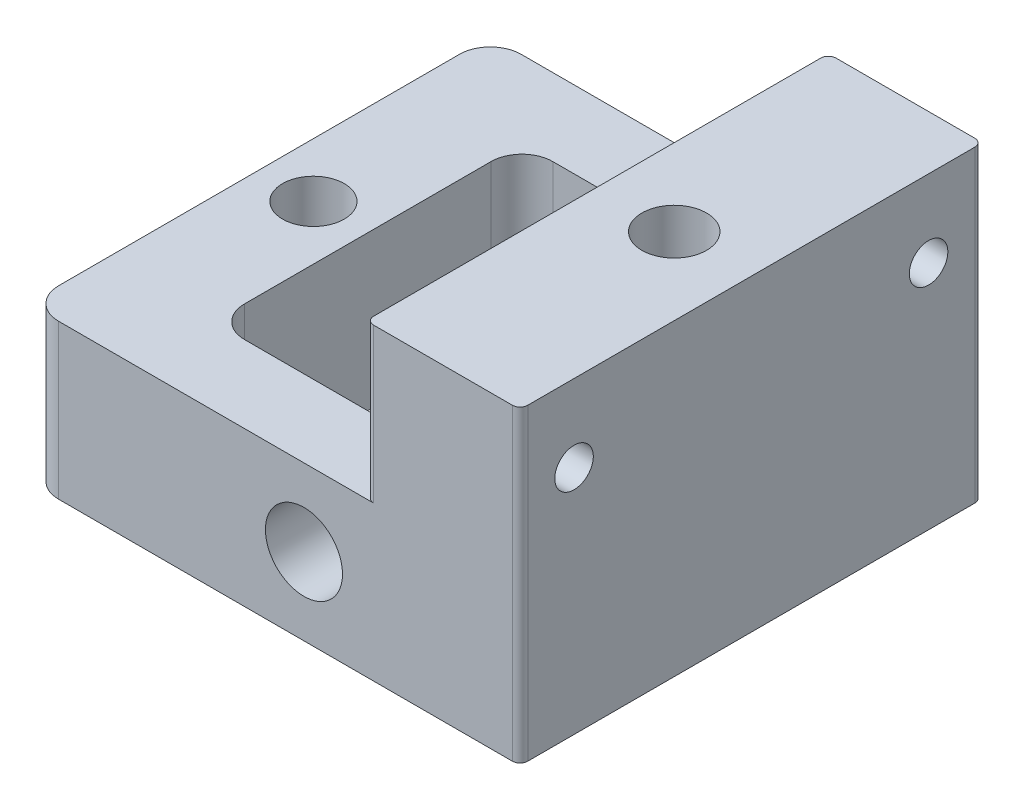
SolidWorks part; units mm, degrees
material "AISI 1045 Steel, cold drawn"
ref_plane "Front Plane" through (0, 0, 0) normal (0, 0, 1) x (1, 0, 0)
ref_plane "Top Plane" through (0, 0, 0) normal (0, 1, 0) x (1, 0, 0)
ref_plane "Right Plane" through (0, 0, 0) normal (1, 0, 0) x (0, 0, -1)
sketch "Sketch1" plane through (0, 0, 0) normal (0, 1, 0) x (1, 0, 0)
  line L1 (7.44, -10) -> (-7.44, -10)
  line L2 (7.44, -10) -> (7.44, 10)
  line L3 (7.44, 10) -> (-7.44, 10)
  line L4 (-7.44, -10) -> (-7.44, 10)
  line L5 (7.44, -10) -> (-7.44, 10) construction
  line L6 (7.44, 10) -> (-7.44, -10) construction
  line L7 (17.44, -15) -> (-14.49, -15)
  line L8 (17.44, -15) -> (17.44, 15)
  line L9 (17.44, 15) -> (-14.49, 15)
  line L10 (-14.49, -15) -> (-14.49, 15)
  line L11 (17.44, -15) -> (-14.49, 15) construction
  line L12 (17.44, 15) -> (-14.49, -15) construction
  point P0 (0, 0)
  point P6 (1.475, 0)
  dimension "D1" = 14.88
  dimension "D2" = 20
  dimension "D3" = 7.05
  dimension "D4" = 5
  dimension "D5" = 10
extrude "Boss-Extrude1" add sketch "Sketch1" along normal blind 10
sketch "Sketch2" plane through (0, 10, 0) normal (0, 1, 0) x (1, 0, 0)
  line L0 (-14.49, -15) -> (17.44, -15) construction
  line L1 (17.44, 15) -> (7.44, 15)
  line L2 (17.44, 15) -> (17.44, -15)
  line L3 (17.44, -15) -> (7.44, -15)
  line L4 (7.44, 15) -> (7.44, -15)
  line L5 (7.44, -10) -> (7.44, 10) construction
extrude "Boss-Extrude2" add sketch "Sketch2" along normal blind 10
hole_wizard "Tap Drill for M5x0.8 Tap1" positions "Sketch3" profile "Sketch4" hole size "M5x0.8" standard "ANSI Metric" end condition through all
sketch "Sketch3" plane through (0, 20, 0) normal (0, 1, 0) x (1, 0, 0)
  line L1 (17.44, 15) -> (7.44, -15) construction
  point P0 (12.44, 0)
sketch "Sketch4" plane through (12.44, 20, 0) normal (1, 0, 0) x (0, 0, 1)
  line L0 (0, 0) -> (0, 20)
  line L1 (0, 20) -> (2.1, 20)
  line L2 (2.1, 20) -> (2.1, 0)
  line L5 (2.1, 0) -> (0, 0)
  line L11 (0, -6.35) -> (0, 107.95) construction
  dimension "Thru Hole Dia." = 4.2
  dimension "Thru Hole Depth" = 20
fillet "Fillet2" radius 2 4 edges at (-7.44, 5, 10) (-7.44, 5, -10) (7.44, 5, -10) (7.44, 5, 10)
sketch "Sketch5" plane through (0, 0, -10) normal (0, 0, 1) x (1, 0, 0)
  line L0 (7.44, 10) -> (7.44, 0) construction
  line L1 (5.44, 10) -> (-5.44, 10) construction
  circle A0 centre (3.42, 5) radius 2.5
  dimension "D2" = 5
  dimension "D1" = 4.02
  dimension "D3" = 5
extrude "Cut-Extrude2" cut sketch "Sketch5" along normal through all
hole_wizard "Tap Drill for M4x0.7 Tap1" positions "Sketch6" profile "Sketch7" hole size "M4x0.7" standard "ANSI Metric" end condition through all
sketch "Sketch6" plane through (0, 0, -10) normal (0, 0, 1) x (1, 0, 0)
  point P0 (3.42, 5)
sketch "Sketch7" plane through (3.42, 5, -10) normal (1, 0, 0) x (0, -1, 0)
  line L0 (0, 0) -> (0, 5)
  line L1 (0, 5) -> (1.65, 5)
  line L2 (1.65, 5) -> (1.65, 0)
  line L5 (1.65, 0) -> (0, 0)
  line L11 (0, -6.35) -> (0, 107.95) construction
  dimension "Thru Hole Dia." = 3.3
  dimension "Thru Hole Depth" = 5
fillet "Fillet3" radius 2 2 edges at (-14.49, 5, -15) (-14.49, 5, 15)
fillet "Fillet4" radius 0.5 4 edges at (17.44, 10, 15) (17.44, 10, -15) (7.44, 15, -15) (7.44, 15, 15)
hole_wizard "Tap Drill for M3x0.5 Tap1" positions "Sketch8" profile "Sketch9" hole size "M3x0.5" standard "ANSI Metric" end condition through all
sketch "Sketch8" plane through (7.44, 0, 0) normal (-1, 0, 0) x (0, 0, 1)
  line L0 (-11.5, 15) -> (11.5, 15) construction
  line L2 (-14.5, 20) -> (14.5, 20) construction
  line L3 (-14.5, 20) -> (-14.5, 10) construction
  point P1 (-11.5, 15)
  point P2 (11.5, 15)
  point P7 (0, 20)
  point P8 (0, 15)
  point P11 (-14.5, 15)
  dimension "D1" = 23
sketch "Sketch9" plane through (7.44, 15, -11.5) normal (0, 1, 0) x (0, 0, 1)
  line L0 (0, 0) -> (0, 10)
  line L1 (0, 10) -> (1.25, 10)
  line L2 (1.25, 10) -> (1.25, 0)
  line L5 (1.25, 0) -> (0, 0)
  line L11 (0, -6.35) -> (0, 107.95) construction
  dimension "Thru Hole Dia." = 2.5
  dimension "Thru Hole Depth" = 10
hole_wizard "Ø4.0 (4) Diameter Hole1" positions "Sketch10" profile "Sketch11" hole size "Ø4.0" standard "ANSI Metric" end condition through all
sketch "Sketch10" plane through (0, 10, 0) normal (0, 1, 0) x (1, 0, 0)
  line L0 (-14.49, 0) -> (-7.44, 0) construction
  line L1 (-14.49, 13) -> (-14.49, -13) construction
  line L2 (-7.44, 8) -> (-7.44, -8) construction
  point P0 (-10.965, 0)
  point P14 (-10.965, 0)
sketch "Sketch11" plane through (-10.965, 10, 0) normal (1, 0, 0) x (0, 0, 1)
  line L0 (0, 0) -> (0, 10)
  line L1 (0, 10) -> (2, 10)
  line L2 (2, 10) -> (2, 0)
  line L5 (2, 0) -> (0, 0)
  line L11 (0, -6.35) -> (0, 107.95) construction
  dimension "Thru Hole Dia." = 4
  dimension "Thru Hole Depth" = 10
